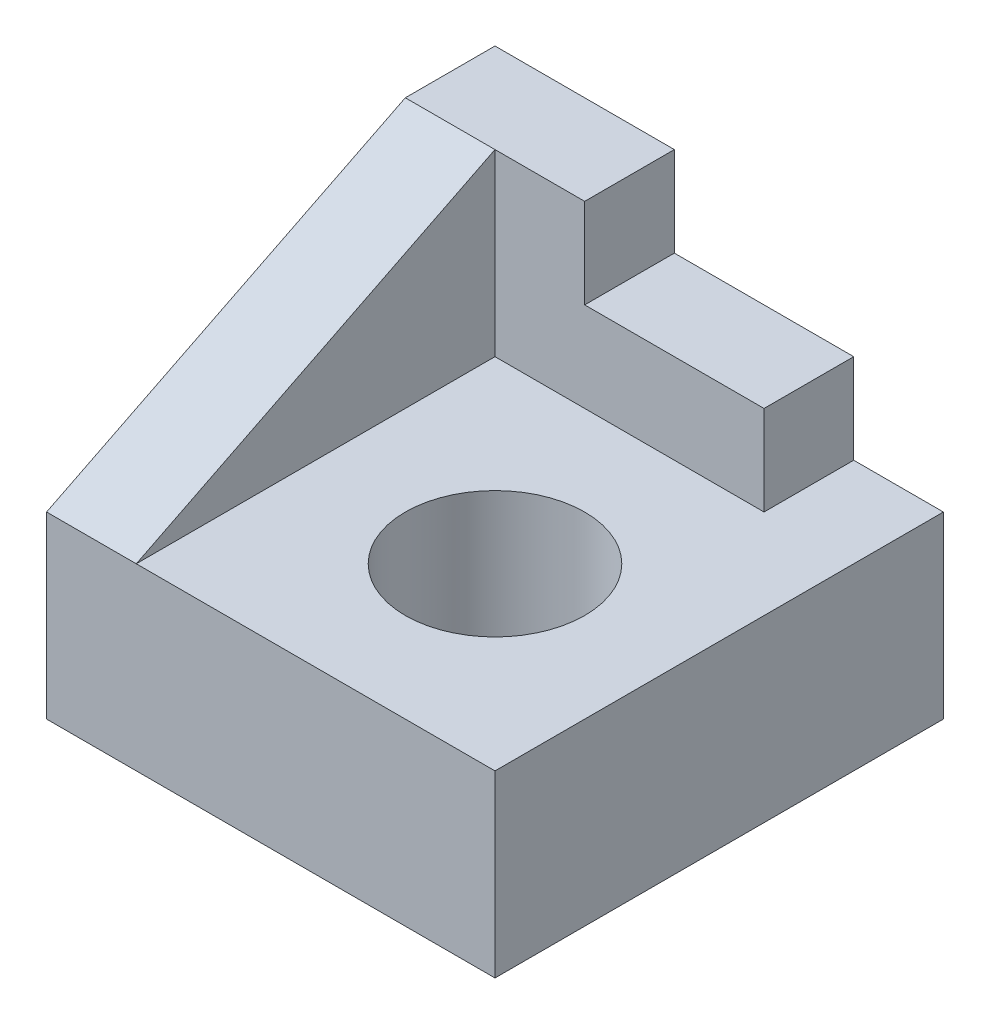
SolidWorks part; units mm, degrees
ref_plane "前基準面" through (0, 0, 0) normal (0, 0, 1) x (1, 0, 0)
ref_plane "上基準面" through (0, 0, 0) normal (0, 1, 0) x (1, 0, 0)
ref_plane "右基準面" through (0, 0, 0) normal (1, 0, 0) x (0, 0, -1)
sketch "草圖1" plane through (0, 0, 0) normal (0, 1, 0) x (1, 0, 0)
  line L1 (-15, 15) -> (10, 15)
  line L2 (-15, 15) -> (-15, -10)
  line L3 (-15, -10) -> (10, -10)
  line L4 (10, 15) -> (10, -10)
  line L5 (-15, 15) -> (-5, 15)
  line L6 (-15, 15) -> (-15, 10)
  line L7 (-15, 10) -> (-5, 10)
  line L8 (-5, 15) -> (-5, 10)
  line L9 (-5, 10) -> (5, 10)
  line L10 (-5, 10) -> (-5, 15)
  line L11 (-5, 15) -> (5, 15)
  line L12 (5, 10) -> (5, 15)
  line L13 (-15, 10) -> (-10, 10)
  line L14 (-15, 10) -> (-15, -10)
  line L15 (-15, -10) -> (-10, -10)
  line L16 (-10, 10) -> (-10, -10)
  circle A0 centre (0, 0) radius 5
  dimension "D9" = 10
  dimension "D1" = 10
  dimension "D2" = 10
  dimension "D3" = 25
  dimension "D4" = 25
  dimension "D5" = 5
  dimension "D6" = 10
  dimension "D7" = 10
  dimension "D8" = 5
extrude "填料-伸長1" add sketch "草圖1" along normal blind 10 contours L7 L16 L3 L4 L1 L12 L9 A0 region at (7.5, 0, -14.6798)
extrude "填料-伸長2" add sketch "草圖1<3>" along normal blind 15 contours L9 L12 L1 L8 region at (0, 0, -12.5)
sketch "草圖1<3>" plane through (0, 0, 0) normal (0, 1, 0) x (1, 0, 0) same geometry as "草圖1"
extrude "填料-伸長3" add sketch "草圖1<4>" along normal blind 20 contours L8 L1 L2 L7 | L16 L7 L2 L3 region at (-10, 0, -12.5) region at (-12.5, 0, 0)
sketch "草圖1<4>" plane through (0, 0, 0) normal (0, 1, 0) x (1, 0, 0) same geometry as "草圖1"
sketch "草圖2" plane through (-10, 0, 0) normal (1, 0, 0) x (0, 0, -1)
  line L0 (-10, 10) -> (10, 20)
  line L1 (-10, 20) -> (-10, 10) construction
  line L2 (10, 20) -> (-10, 20) construction
  line L3 (10, 20) -> (-10, 20)
  line L4 (-10, 20) -> (-10, 10)
  point P8 (10, 20)
  dimension "D1" = 10
extrude "除料-伸長1" cut sketch "草圖2" against normal blind 20
